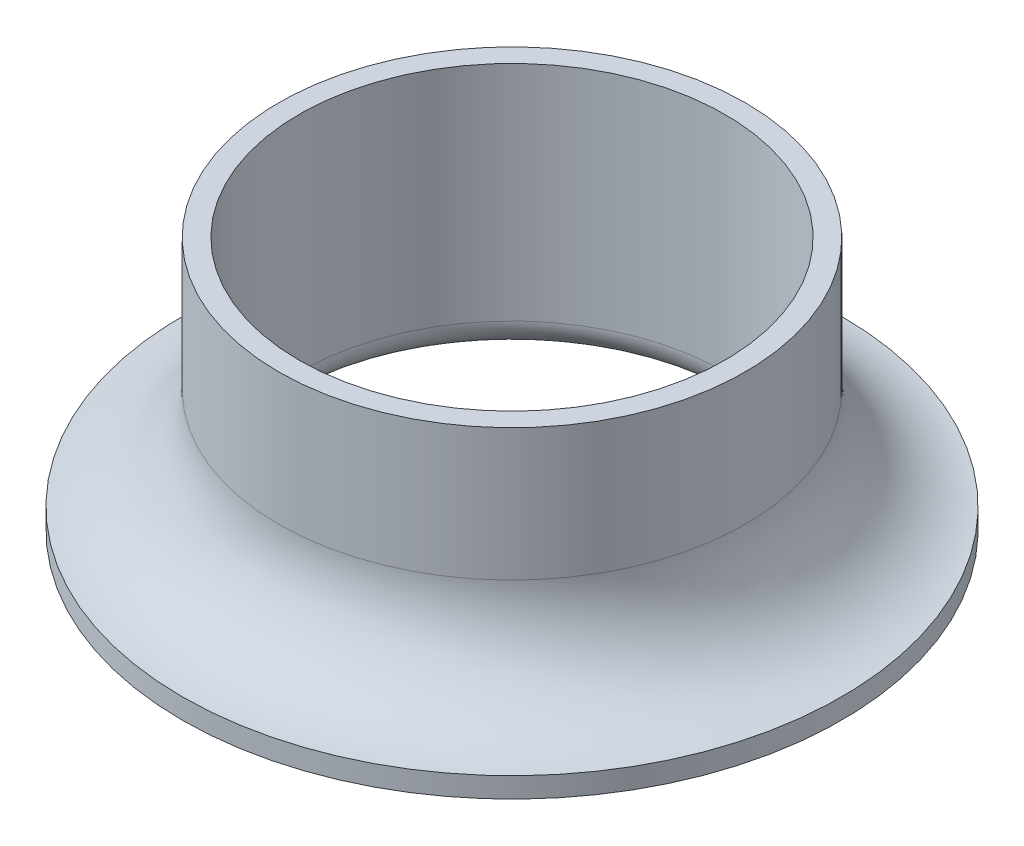
SolidWorks part; units mm, degrees
ref_plane "Front Plane" through (0, 0, 0) normal (0, 0, 1) x (1, 0, 0)
ref_plane "Top Plane" through (0, 0, 0) normal (0, 1, 0) x (1, 0, 0)
ref_plane "Right Plane" through (0, 0, 0) normal (1, 0, 0) x (0, 0, -1)
sketch "Sketch1" plane through (0, 0, 0) normal (0, 1, 0) x (1, 0, 0)
  circle A0 centre (0, 0) radius 21
  circle A1 centre (0, 0) radius 23
  dimension "D1" = 42
  dimension "D2" = 2
extrude "Boss-Extrude1" add sketch "Sketch1" along normal blind 25
sketch "Sketch2" plane through (0, 0, 0) normal (0, 1, 0) x (1, 0, 0)
  circle A0 centre (0, 0) radius 23 construction
  circle A1 centre (0, 0) radius 23
  circle A2 centre (0, 0) radius 32.5
  dimension "D1" = 65
extrude "Boss-Extrude2" add sketch "Sketch2" along normal blind 2
fillet "Fillet1" radius 10 1 edges at (0, 2, 23)
fillet "Fillet2" radius 3 1 edges at (0, 0, 21)
